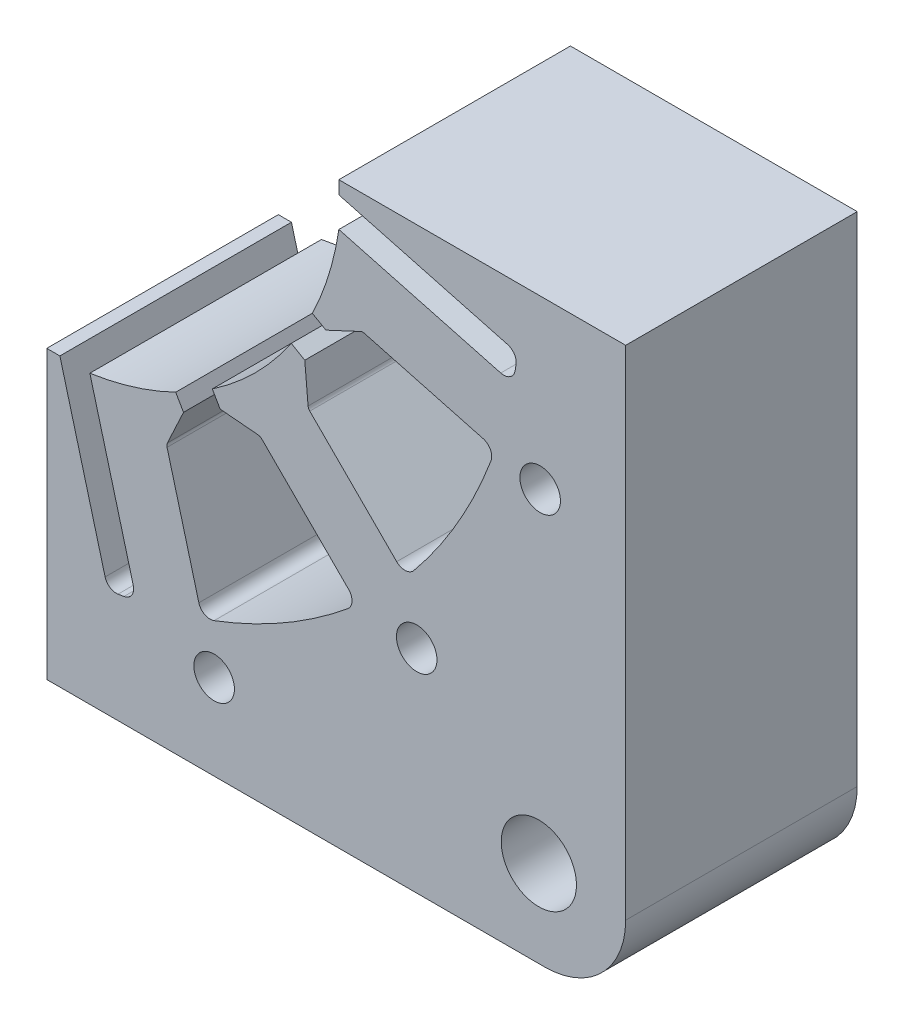
SolidWorks part; units mm, degrees
ref_plane "Front" through (0, 0, 0) normal (0, 0, 1) x (1, 0, 0)
ref_plane "Top" through (0, 0, 0) normal (0, 1, 0) x (1, 0, 0)
ref_plane "Right" through (0, 0, 0) normal (1, 0, 0) x (0, 0, -1)
sketch "Sketch1" plane through (0, 0, 0) normal (0, 0, 1) x (1, 0, 0)
  line L1 (-50, 50) -> (50, 50)
  line L2 (-50, 50) -> (-50, -50)
  line L3 (-50, -50) -> (50, -50)
  line L4 (50, 50) -> (50, -50)
  circle A0 centre (0, 0) radius 50 construction
  circle A1 centre (0, 0) radius 25.5
  dimension "D1" = 100
  dimension "D2" = 51
extrude "Lamination Extruction" add sketch "Sketch1" along normal blind 20
ref_axis "Axis1" through (0, 0, 20) along (0, 0, -1)
sketch "Sketch2" plane through (0, 0, 20) normal (0, 0, 1) x (1, 0, 0)
  line L0 (0, 0) -> (0, 50) construction
  line L1 (50, 50) -> (-50, 50) construction
  line L2 (-1.825, 26.7846) -> (1.825, 26.7846) construction
  line L3 (7.75, 40.2609) -> (4.6735, 28.7791)
  line L4 (4.6735, 28.7791) -> (1.825, 26.7846)
  line L5 (-1.825, 26.7846) -> (-1.825, 25.4346)
  line L6 (-7.75, 40.2609) -> (-4.6735, 28.7791)
  line L7 (-4.6735, 28.7791) -> (-1.825, 26.7846)
  line L8 (1.825, 26.7846) -> (1.825, 25.4346)
  line L9 (-4.6735, 28.7791) -> (4.6735, 28.7791) construction
  arc A1 (-7.75, 40.2609) -> (7.75, 40.2609) centre (0, 0) cw
  circle A3 centre (0, 0) radius 25.5 construction
  arc A4 (1.825, 25.4346) -> (-1.825, 25.4346) centre (0, 0) ccw
  point P7 (0, 26.7846)
  point P16 (0, 41)
  point P19 (0, 28.7791)
  circle M15 centre (0, 0) radius 25.5
  dimension "D2" = 41
  dimension "D1" = 30
  dimension "D3" = 15.5
  dimension "D6" = 35
  dimension "D4" = 1.35
  dimension "D5" = 3.65
extrude "Slot Cut" cut sketch "Sketch2" against normal through all contours A1 L6 L7 L5 L8 L4 L3 M15 region at (0, 34.4506, 20)
fillet "Slot Fillet Top" radius 1 2 edges at (7.75, 40.2609, 10) (-7.75, 40.2609, 10)
fillet "Slot Fillet Bottom" radius 0.5 2 edges at (4.6735, 28.7791, 10) (-4.6735, 28.7791, 10)
pattern_circular "Slot Duplicate" count 12 over 360 about axis through (0, 0, 20) along (0, 0, -1) of "Slot Cut", "Slot Fillet Top", "Slot Fillet Bottom"
sketch "Sketch3" plane through (0, 0, 20) normal (0, 0, 1) x (1, 0, 0)
  line L1 (42.5, 42.5) -> (-42.5, 42.5) construction
  line L2 (42.5, 42.5) -> (42.5, -42.5) construction
  line L3 (42.5, -42.5) -> (-42.5, -42.5) construction
  line L4 (-42.5, 42.5) -> (-42.5, -42.5) construction
  line L5 (42.5, 42.5) -> (-42.5, -42.5) construction
  line L6 (42.5, -42.5) -> (-42.5, 42.5) construction
  circle A1 centre (-42.5, 42.5) radius 3.25
  circle A2 centre (42.5, 42.5) radius 3.25
  circle A3 centre (42.5, -42.5) radius 3.25
  circle A4 centre (-42.5, -42.5) radius 3.25
  point P0 (0, 0)
  dimension "D2" = 6.5
  dimension "D1" = 85
extrude "Bolt Hole Cut" cut sketch "Sketch3" against normal through all
fillet "Corner Fillet" radius 7 4 edges at (-50, 50, 10) (-50, -50, 10) (50, -50, 10) (50, 50, 10)
sketch "Sketch4" plane through (0, 0, 20) normal (0, 0, 1) x (1, 0, 0)
  line L0 (-50, 43) -> (-50, -43) construction
  line L1 (-50, -50) -> (0, -50)
  line L2 (-50, -50) -> (-50, 50)
  line L3 (-50, 50) -> (0, 50)
  line L4 (0, -50) -> (0, 50)
  line L6 (43, 50) -> (-43, 50) construction
  line L7 (-43, -50) -> (43, -50) construction
extrude "Cut-Extrude1" cut sketch "Sketch4" against normal through all
sketch "Sketch5" plane through (0, 0, 20) normal (0, 0, 1) x (1, 0, 0)
  line L0 (50, -43) -> (50, 43) construction
  line L1 (0, 50) -> (50, 50)
  line L2 (0, 50) -> (0, 0)
  line L3 (0, 0) -> (50, 0)
  line L4 (50, 50) -> (50, 0)
extrude "Cut-Extrude2" cut sketch "Sketch5" against normal through all
sketch "Sketch6" plane through (0, 0, 20) normal (0, 0, 1) x (1, 0, 0)
  line L0 (41, 0) -> (50, 0) construction
  line L1 (0, -50) -> (0, -41) construction
  line L2 (13.1369, -37.6902) -> (10.3893, -27.436) construction
  line L3 (37.6902, -13.1369) -> (27.436, -10.3893) construction
  circle A0 centre (42.6147, -14.4564) radius 1.75
  circle A1 centre (14.4564, -42.6147) radius 1.75
  arc A2 (45, 0) -> (0, -45) centre (0, 0) cw construction
  circle A3 centre (31.9536, -31.6855) radius 1.75
  dimension "D1" = 45
  dimension "D2" = 3.5
extrude "Cut-Extrude3" cut sketch "Sketch6" against normal through all
sketch "Sketch7" plane through (0, 0, 0) normal (0, 0, -1) x (-1, 0, 0)
  line L0 (-7.4682, -39.2091) -> (-3.7217, -25.227)
  line L1 (-7.4682, -39.2091) -> (-4.7206, -28.9549) construction
  line L2 (-39.2091, -7.4682) -> (-25.227, -3.7217)
  line L3 (-39.2091, -7.4682) -> (-28.9549, -4.7206) construction
  line L4 (-25.227, -3.7217) -> (-25.227, 0)
  line L5 (-25.227, 0) -> (-41, 0)
  line L6 (-3.7217, -25.227) -> (0, -25.227)
  line L7 (0, -25.227) -> (0, -41)
  line L8 (0, -41) -> (-7.4682, -39.2091)
  line L9 (-41, 0) -> (-39.2091, -7.4682)
  arc A0 (-11.1368, -22.9395) -> (-1.825, -25.4346) centre (0, 0) ccw construction
  arc A1 (-25.4346, -1.825) -> (-22.9395, -11.1368) centre (0, 0) ccw construction
extrude "Cut-Extrude4" cut sketch "Sketch7" against normal through all
sketch "Sketch8" plane through (0, 0, 0) normal (0, 0, -1) x (-1, 0, 0)
  line L0 (-25.227, -1.1335) -> (-40.6601, -5.2688)
  line L1 (-39.2091, -7.4682) -> (-25.227, -3.7217) construction
  line L2 (-25.227, 0) -> (-25.227, -1.1335)
  line L3 (-25.227, 0) -> (-41, 0)
  line L4 (0, -41) -> (0, -25.227)
  line L5 (0, -25.227) -> (-1.1335, -25.227)
  line L6 (-1.1335, -25.227) -> (-5.2688, -40.6601)
  line L7 (-7.4682, -39.2091) -> (-3.7217, -25.227) construction
  arc A0 (-41, 0) -> (-40.4547, -6.6648) centre (0, 0) ccw construction
  arc A1 (-41, 0) -> (-40.6601, -5.2688) centre (0, 0) ccw
  arc A2 (-6.6648, -40.4547) -> (0, -41) centre (0, 0) ccw construction
  arc A3 (-5.2688, -40.6601) -> (0, -41) centre (0, 0) ccw
  dimension "D1" = 2.5
  dimension "D2" = 2.5
extrude "Boss-Extrude1" add sketch "Sketch8" against normal up to surface (20 mm away) up to face at (23.0121, -23.0121, 20)
fillet "Fillet1" radius 1 2 edges at (5.2688, -40.6601, 10) (40.6601, -5.2688, 10)
equation "\"DS1\"= 100mm"
equation "\"D1@Sketch1\"=\"DS1\""
equation "\"DS2\"=51"
equation "\"D2@Sketch1\"=\"DS2\""
equation "\"HEIGHT\"=20"
equation "\"D1@Lamination Extruction\" = \"HEIGHT\""
equation "\"AngSlot\"=30"
equation "\"D1@Sketch2\"=\"AngSlot\""
equation "\"DSS\"= 15.5mm"
equation "\"D2@Sketch2\"=\"DSS\"+\"DS2\"/2"
equation "\"WSSB\"=15.5"
equation "\"D3@Sketch2\"=\"WSSB\""
equation "\"WSSO\"=3.65"
equation "\"HSTT\"=1.35"
equation "\"AngSTT\"=35"
equation "\"D6@Sketch2\"=\"AngSTT\""
equation "\"D4@Sketch2\"=\"HSTT\""
equation "\"D5@Sketch2\"=\"WSSO\""
equation "\"FRSSB\"=1"
equation "\"D1@Slot Fillet Top\" = \"FRSSB\""
equation "\"FRSST\"=0.5"
equation "\"D1@Slot Fillet Bottom\" = \"FRSST\""
equation "\"SLOTS\"=12"
equation "\"D1@Slot Duplicate\" = \"SLOTS\""
equation "\"HOLE_BOLT\"= 85"
equation "\"D1@Sketch3\"=\"HOLE_BOLT\""
equation "\"BOLT_DIA\"=6.5"
equation "\"D2@Sketch3\"=\"BOLT_DIA\""
equation "\"LAM_FILLET\"=7"
equation "\"D1@Corner Fillet\"=\"LAM_FILLET\""
